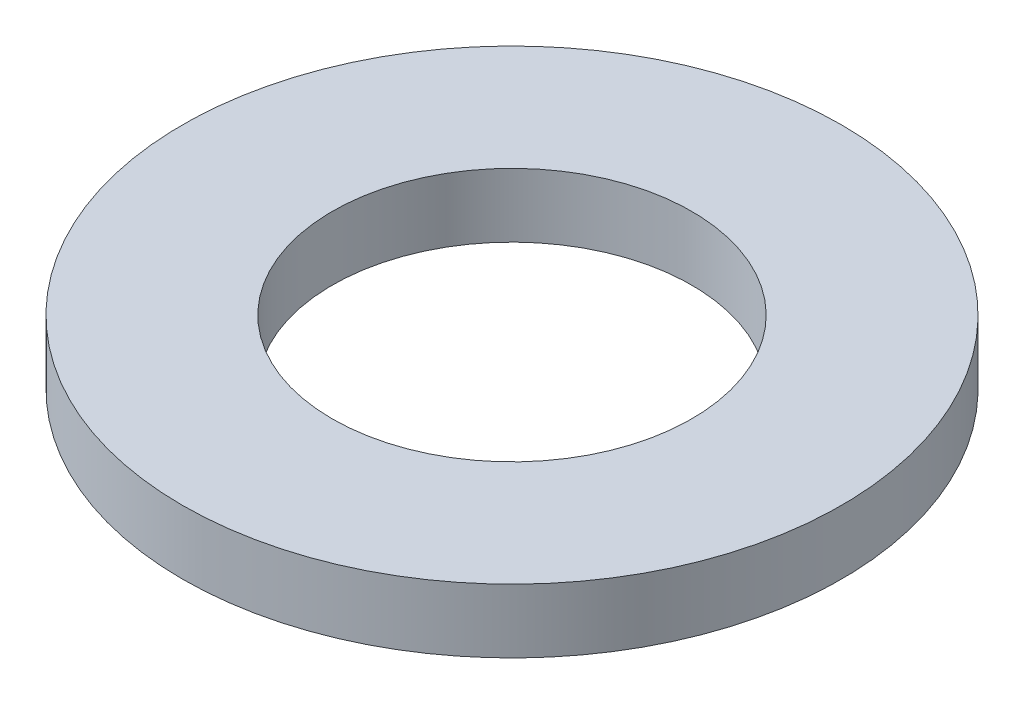
SolidWorks part; units mm, degrees
ref_plane "Front Plane" through (0, 0, 0) normal (0, 0, 1) x (1, 0, 0)
ref_plane "Top Plane" through (0, 0, 0) normal (0, 1, 0) x (1, 0, 0)
ref_plane "Right Plane" through (0, 0, 0) normal (1, 0, 0) x (0, 0, -1)
sketch "Sketch1" plane through (0, 0, 0) normal (0, 1, 0) x (1, 0, 0)
  circle A0 centre (0, 0) radius 82.5
  dimension "FLANGE_OD" = 165
extrude "Boss-Extrude1" add sketch "Sketch1" along normal blind 16
sketch "Sketch2" plane through (0, 0, 0) normal (0, 1, 0) x (1, 0, 0)
  circle A0 centre (0, 0) radius 45
  dimension "BORE_D" = 90
extrude "Cut-Extrude1" cut sketch "Sketch2" along normal through all
sketch "Sketch3" plane through (0, 16, 0) normal (0, 1, 0) x (1, 0, 0)
  circle A0 centre (0, 0) radius 38.7684 construction
  circle A1 centre (-38.7684, 0) radius 2.5956
  dimension "BOLT_D" = 5.1913
  dimension "BOLT_PCD" = 77.5369
extrude "Cut-Extrude2" cut sketch "Sketch3" against normal blind 14.4318 rebuild error yes
pattern_circular "CirPattern1" count 8 over 360 rebuild error yes
